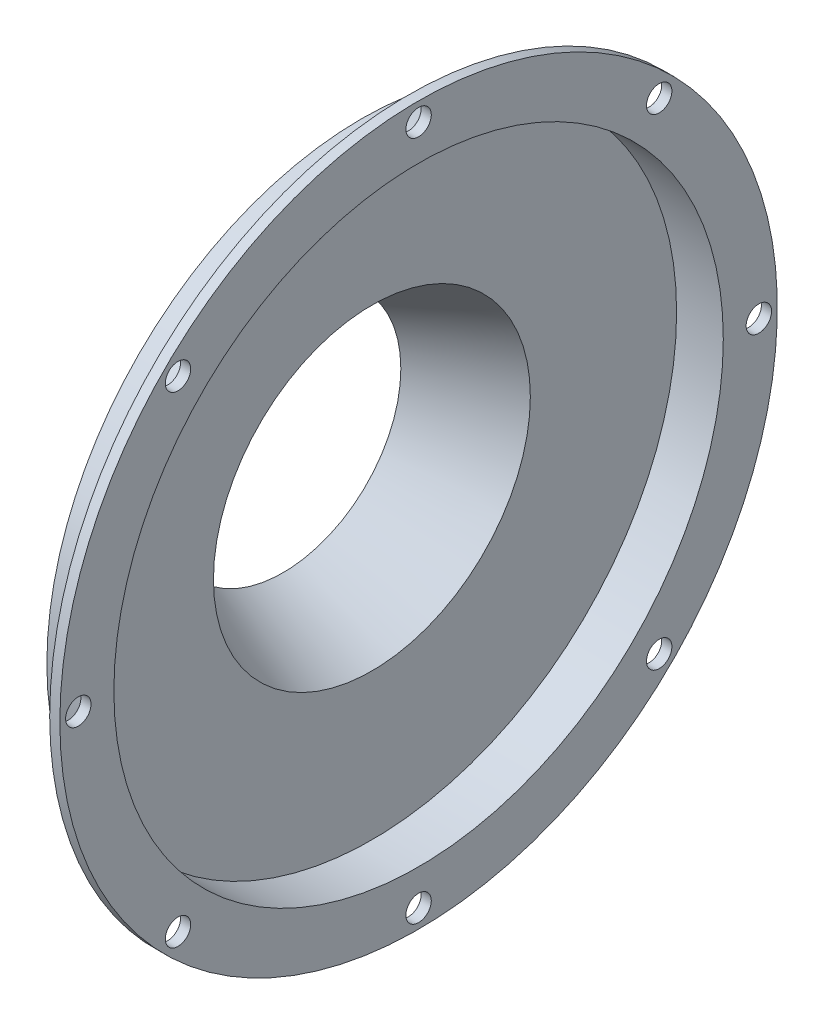
SolidWorks part; units mm, degrees
ref_plane "Front Plane" through (0, 0, 0) normal (0, 0, 1) x (1, 0, 0)
ref_plane "Top Plane" through (0, 0, 0) normal (0, 1, 0) x (1, 0, 0)
ref_plane "Right Plane" through (0, 0, 0) normal (1, 0, 0) x (0, 0, -1)
sketch "Sketch1" plane through (0, 0, 0) normal (0, 0, 1) x (1, 0, 0)
  line L0 (0, 0) -> (61.3012, 0) construction
  line L1 (0, 29.464) -> (22.225, 39.624)
  line L2 (22.225, 39.624) -> (22.225, 76.2)
  line L3 (22.225, 76.2) -> (33.9014, 76.2)
  line L4 (33.9014, 76.2) -> (33.9014, 89.7128)
  line L5 (-1.056, 31.7741) -> (19.685, 41.2557)
  line L6 (19.685, 41.2557) -> (19.685, 78.74)
  line L7 (19.685, 78.74) -> (31.3614, 78.74)
  line L8 (31.3614, 78.74) -> (31.3614, 89.7128)
  line L9 (-1.056, 31.7741) -> (0, 29.464)
  line L10 (31.3614, 89.7128) -> (33.9014, 89.7128)
  point P5 (30.6506, 0)
  dimension "D1" = 29.464
  dimension "D2" = 39.624
  dimension "D3" = 22.225
  dimension "D4" = 76.2
  dimension "D5" = 89.7128
  dimension "D6" = 2.54
revolve "Revolve1" add sketch "Sketch1" angle 360 about L0
sketch "Sketch2" plane through (31.3614, 0, 0) normal (-1, 0, 0) x (0, 0, 1)
  circle A0 centre (0, 85.09) radius 3.175
  dimension "D1" = 6.35
  dimension "D2" = 85.09
extrude "Cut-Extrude1" cut sketch "Sketch2" against normal blind 2.54
pattern_circular "CirPattern1" count 8 over 360 about axis through (31.3614, 0, 0) along (-1, 0, 0) of "Cut-Extrude1"
